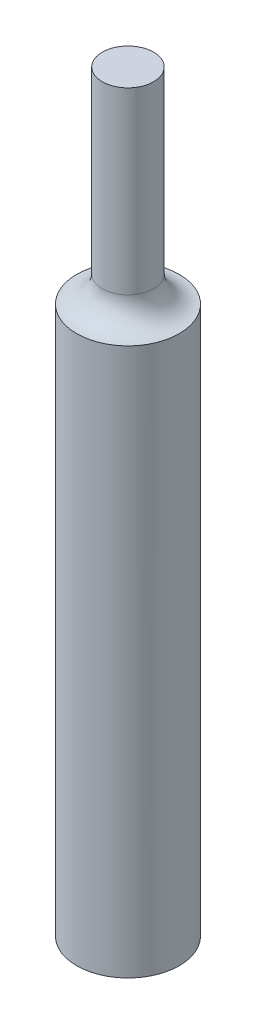
SolidWorks part; units mm, degrees
ref_plane "Front Plane" through (0, 0, 0) normal (0, 0, 1) x (1, 0, 0)
ref_plane "Top Plane" through (0, 0, 0) normal (0, 1, 0) x (1, 0, 0)
ref_plane "Right Plane" through (0, 0, 0) normal (1, 0, 0) x (0, 0, -1)
sketch "Sketch1" plane through (0, 0, 0) normal (0, 1, 0) x (1, 0, 0)
  circle A0 centre (0, 0) radius 19.05
  dimension "D1" = 38.1
extrude "Boss-Extrude1" add sketch "Sketch1" along normal blind 203.2
sketch "Sketch2" plane through (0, 203.2, 0) normal (0, 1, 0) x (1, 0, 0)
  circle A0 centre (0, 0) radius 9.525
  dimension "D1" = 19.05
extrude "Boss-Extrude2" add sketch "Sketch2" along normal blind 76.2
fillet "Fillet1" radius 9.652 1 edges at (0, 203.2, 9.525)
